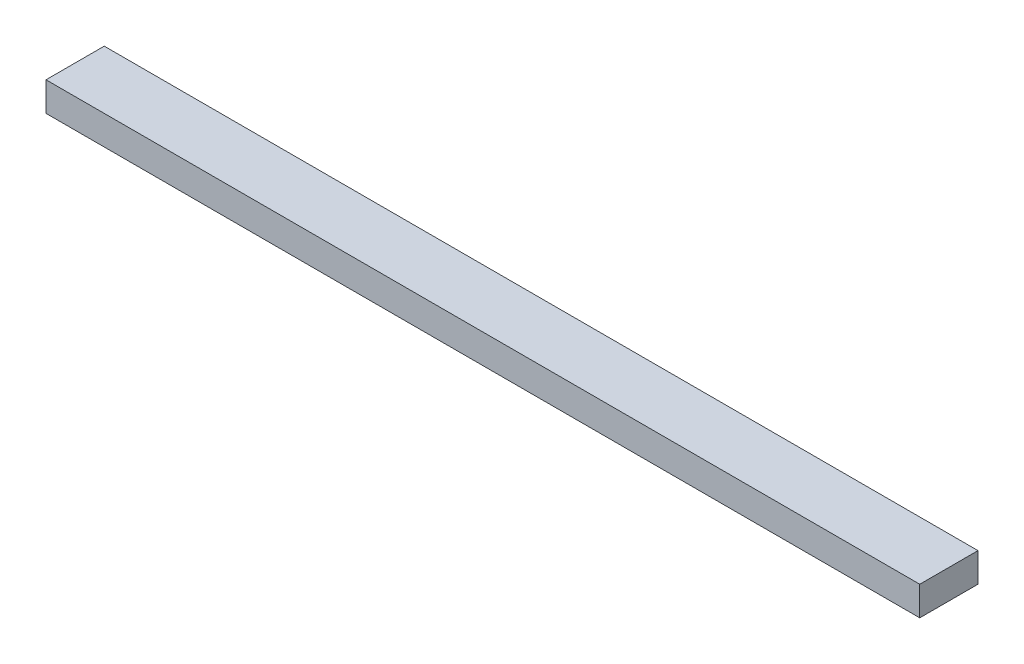
SolidWorks part; units mm, degrees
ref_plane "前视基准面" through (0, 0, 0) normal (0, 0, 1) x (1, 0, 0)
ref_plane "上视基准面" through (0, 0, 0) normal (0, 1, 0) x (1, 0, 0)
ref_plane "右视基准面" through (0, 0, 0) normal (1, 0, 0) x (0, 0, -1)
sketch "草图1" plane through (0, 0, 0) normal (0, 1, 0) x (1, 0, 0)
  line L0 (0, 0) -> (150, 0)
  line L1 (150, 0) -> (150, -10)
  line L2 (150, -10) -> (0, -10)
  line L3 (0, -10) -> (0, 0)
extrude "凸台-拉伸1" add sketch "草图1" along normal blind 5
